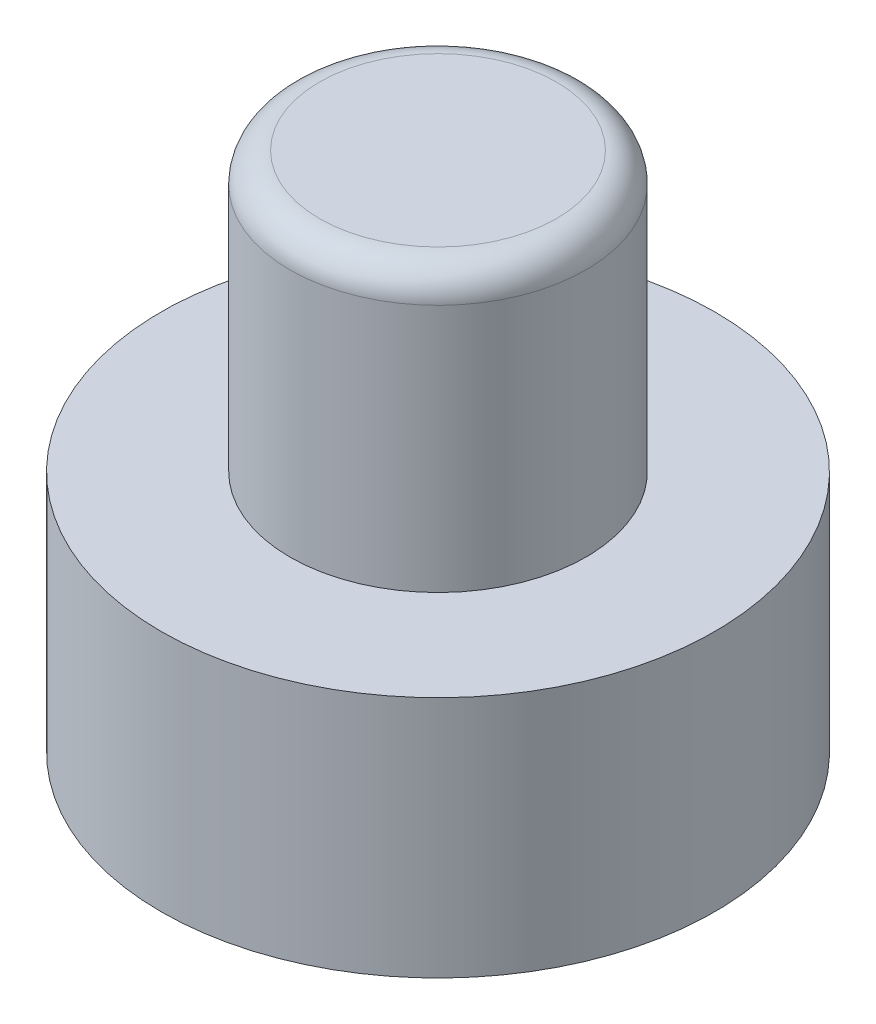
SolidWorks part; units mm, degrees
ref_plane "Front Plane" through (0, 0, 0) normal (0, 0, 1) x (1, 0, 0)
ref_plane "Top Plane" through (0, 0, 0) normal (0, 1, 0) x (1, 0, 0)
ref_plane "Right Plane" through (0, 0, 0) normal (1, 0, 0) x (0, 0, -1)
sketch "Sketch1" plane through (0, 0, 0) normal (0, 1, 0) x (1, 0, 0)
  circle A0 centre (0, 0) radius 4.675
  dimension "D1" = 9.35
extrude "Boss-Extrude1" add sketch "Sketch1" along normal blind 4.1
sketch "Sketch2" plane through (0, 4.1, 0) normal (0, 1, 0) x (1, 0, 0)
  circle A0 centre (0, 0) radius 2.5
  dimension "D1" = 5
extrude "Boss-Extrude2" add sketch "Sketch2" along normal blind 4.7
fillet "Fillet1" radius 0.5 1 edges at (0, 8.8, 2.5)
